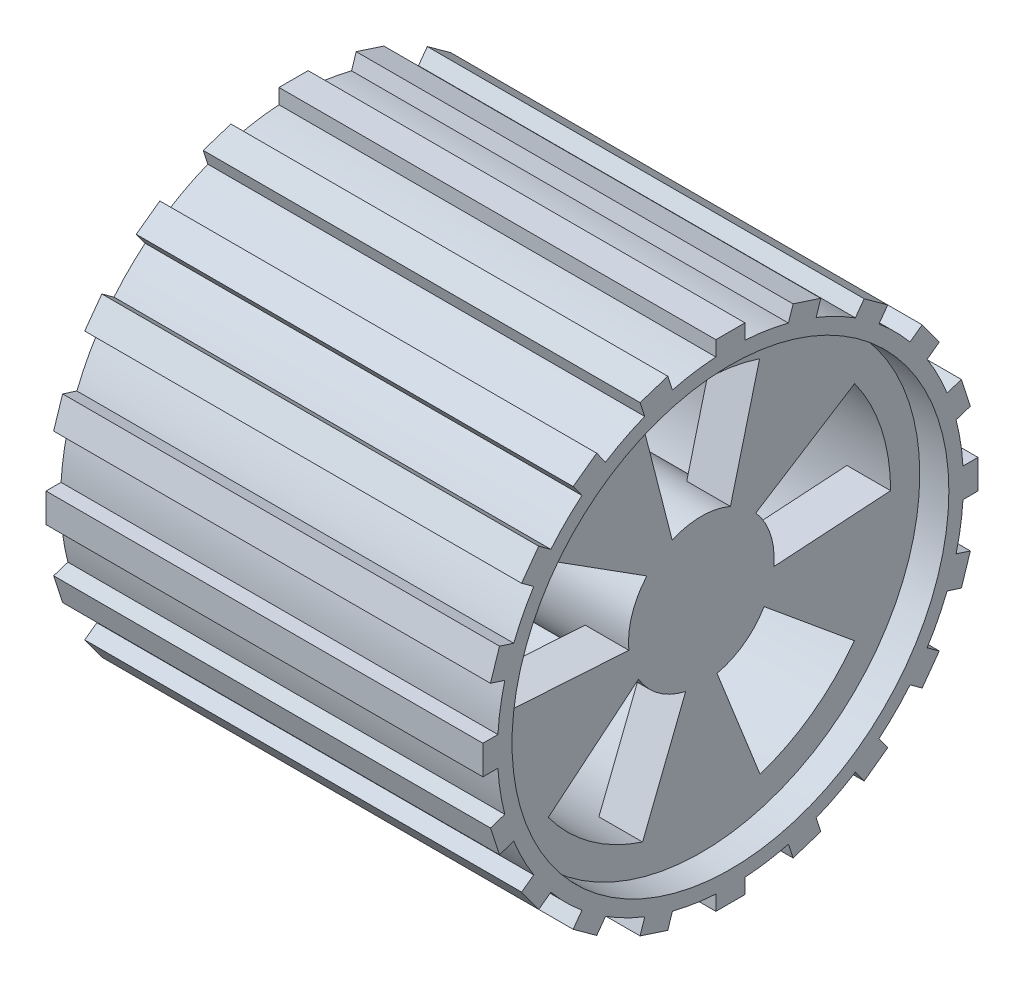
SolidWorks part; units mm, degrees
ref_plane "Front Plane" through (0, 0, 0) normal (0, 0, 1) x (1, 0, 0)
ref_plane "Top Plane" through (0, 0, 0) normal (0, 1, 0) x (1, 0, 0)
ref_plane "Right Plane" through (0, 0, 0) normal (1, 0, 0) x (0, 0, -1)
sketch "Sketch1" plane through (0, 0, 0) normal (1, 0, 0) x (0, 0, -1)
  circle A0 centre (0, 0) radius 16
  dimension "D1" = 32
extrude "Boss-Extrude1" add sketch "Sketch1" along normal blind 30
sketch "Sketch2" plane through (0, 0, 0) normal (-1, 0, 0) x (0, 0, 1)
  circle A0 centre (0, 0) radius 5
  dimension "D1" = 10
extrude "Boss-Extrude2" add sketch "Sketch2" along normal blind 5
sketch "Sketch3" plane through (30, 0, 0) normal (1, 0, 0) x (0, 0, -1)
  line L0 (0, 16) -> (0, -16) construction
  line L1 (-4, 12.3693) -> (-2, 4.5826)
  line L2 (4, 12.3693) -> (2, 4.5826)
  line L3 (10.5279, 7.6266) -> (3.7403, 3.3182)
  line L4 (13, 0.0181) -> (4.9763, -0.486)
  line L5 (10.5066, -7.6558) -> (4.3116, -2.5318)
  line L6 (4.0344, -12.3581) -> (1.0755, -4.883)
  line L7 (-4.0344, -12.3581) -> (-1.0755, -4.883)
  line L8 (-10.5066, -7.6558) -> (-4.3116, -2.5318)
  line L9 (-13, 0.0181) -> (-4.9763, -0.486)
  line L10 (-10.5279, 7.6266) -> (-3.7403, 3.3182)
  circle A0 centre (0, 0) radius 16 construction
  circle A1 centre (0, 0) radius 13
  circle A2 centre (0, 0) radius 5
  circle A3 centre (0, 0) radius 5 construction
  point P31 (0, 0)
  dimension "D1" = 3
  dimension "D2" = 10
  dimension "D3" = 8
  dimension "D4" = 4
  dimension "D5" = 5
extrude "Cut-Extrude1" cut sketch "Sketch3" against normal up to next contours L0 A1 L1 A2 | A1 L0 A2 L2 | A2 L10 A1 L9 | A2 L8 A1 L7 | A2 L6 A1 L5 | A2 L4 A1 L3 region at (30, 9.2602, -1.5704) region at (30, 9.2602, 1.5704) region at (30, 2.8615, -8.8069) region at (30, 2.8615, 8.8069) region at (30, -7.4916, 5.443) region at (30, -7.4916, -5.443)
sketch "Sketch4" plane through (0, 0, 0) normal (-1, 0, 0) x (0, 0, 1)
  circle A0 centre (0, 0) radius 5
  circle A1 centre (0, 0) radius 5 construction
  circle A2 centre (0, 0) radius 13
  circle A3 centre (0, 0) radius 13 construction
extrude "Cut-Extrude2" cut sketch "Sketch4" against normal offset from surface (25 mm away) 5 up to face at (30, -7.0692, -5.1361)
sketch "Sketch5" plane through (30, 0, 0) normal (1, 0, 0) x (0, 0, -1)
  circle A0 centre (0, 0) radius 15
extrude "Cut-Extrude3" cut sketch "Sketch5" against normal blind 2
ref_plane "Plane1" through (0, 16, 0) normal (0, 1, 0) x (1, 0, 0)
ref_plane "Plane2" through (0, 15, 0) normal (0, 1, 0) x (1, 0, 0)
sketch "Sketch6" plane through (0, 15, 0) normal (0, 1, 0) x (1, 0, 0)
  line L0 (0, 0) -> (30, 0) construction
  line L1 (30, -16) -> (30, 16) construction
  line L2 (15, 16) -> (15, -16) construction
  line L3 (30, 16) -> (0, 16) construction
  line L4 (0, -16) -> (30, -16) construction
  line L5 (0, 16) -> (0, -16) construction
  line L6 (30, 1) -> (0, 1)
  line L7 (30, 1) -> (30, -1)
  line L8 (30, -1) -> (0, -1)
  line L9 (0, 1) -> (0, -1)
  line L10 (30, 1) -> (0, -1) construction
  line L11 (30, -1) -> (0, 1) construction
  point P11 (15, 0)
  dimension "D1" = 2
extrude "Boss-Extrude3" add sketch "Sketch6" along normal blind 2
ref_axis "Axis1" through (-5, 0, 0) along (1, 0, 0)
pattern_circular "CirPattern1" count 20 over 360 about axis through (-5, 0, 0) along (1, 0, 0) of "Boss-Extrude3"
